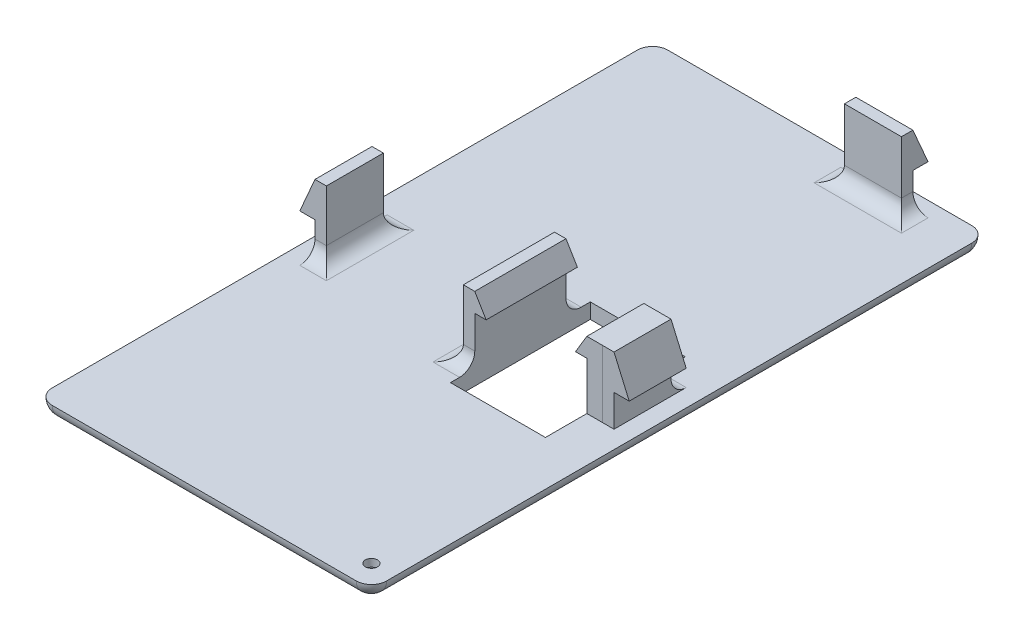
SolidWorks part; units mm, degrees
ref_plane "前视基准面" through (0, 0, 0) normal (0, 0, 1) x (1, 0, 0)
ref_plane "上视基准面" through (0, 0, 0) normal (0, 1, 0) x (1, 0, 0)
ref_plane "右视基准面" through (0, 0, 0) normal (1, 0, 0) x (0, 0, -1)
sketch "草图1" plane through (0, 0, 0) normal (0, 1, 0) x (1, 0, 0)
  line L1 (-22, 43) -> (22, 43)
  line L2 (-22, 43) -> (-22, -38)
  line L3 (-22, -38) -> (22, -38)
  line L4 (22, 43) -> (22, -38)
  dimension "D1" = 44
  dimension "D2" = 81
  dimension "D3" = 22
  dimension "D4" = 43
extrude "凸台-拉伸1" add sketch "草图1" along normal blind 2
fillet "圆角1" radius 2 4 edges at (-22, 0, -2.5) (0, 0, -43) (22, 0, -2.5) (0, 0, 38)
sketch "草图4" plane through (0, 2, 0) normal (0, 1, 0) x (1, 0, 0)
  line L1 (-19.675, 3.75) -> (-18.175, 3.75)
  line L2 (-19.675, 3.75) -> (-19.675, -3.75)
  line L3 (-19.675, -3.75) -> (-18.175, -3.75)
  line L4 (-18.175, 3.75) -> (-18.175, -3.75)
  dimension "D1" = 7.5
  dimension "D2" = 3.75
  dimension "D3" = 1.5
extrude "凸台-拉伸4" add sketch "草图4" along normal blind 8.8
sketch "草图6" plane through (0, 0, 3.75) normal (0, 0, 1) x (1, 0, 0)
  line L0 (-19.675, 10.8) -> (-21.675, 6.2)
  line L1 (-21.675, 6.2) -> (-19.675, 6.2)
  line L2 (-19.675, 10.8) -> (-19.675, 2) construction
  line L3 (-19.675, 6.2) -> (-19.675, 10.8)
  dimension "D1" = 4.6
  dimension "D2" = 2
extrude "凸台-拉伸5" add sketch "草图6" against normal blind 7.5
mirror "镜向2" about plane through (0, 0, 0) normal (1, 0, 0) of "凸台-拉伸4", "凸台-拉伸5"
sketch "草图7" plane through (0, 0, 0) normal (0, -1, 0) x (1, 0, 0)
  line L0 (-20, 38) -> (20, 38) construction
  line L1 (22, 36) -> (22, -41) construction
  circle A0 centre (19, 35) radius 0.8
  dimension "D3" = 1.6
  dimension "D1" = 3
  dimension "D2" = 3
extrude "切除-拉伸1" cut sketch "草图7" against normal blind 8.8
sketch "草图8" plane through (0, 0, 0) normal (0, -1, 0) x (1, 0, 0)
  circle A0 centre (19, 35) radius 2
extrude "切除-拉伸2" cut sketch "草图8" against normal blind 1
sketch "草图10" plane through (0, 2, 0) normal (0, 1, 0) x (1, 0, 0)
  line L0 (22, -36) -> (22, 41) construction
  line L1 (6.75, 41) -> (14.25, 41)
  line L2 (6.75, 41) -> (6.75, 39.5)
  line L3 (6.75, 39.5) -> (14.25, 39.5)
  line L4 (14.25, 41) -> (14.25, 39.5)
  line L5 (20, 43) -> (-20, 43) construction
  dimension "D1" = 7.75
  dimension "D2" = 1.5
  dimension "D3" = 2
  dimension "D4" = 7.5
extrude "凸台-拉伸6" add sketch "草图10" along normal blind 9
sketch "草图11" plane through (14.25, 0, 0) normal (1, 0, 0) x (0, 0, -1)
  line L0 (41, 11) -> (43, 6.4)
  line L1 (43, 6.4) -> (41, 6.4)
  line L2 (41, 11) -> (41, 2) construction
  line L3 (41, 11) -> (41, 6.4)
  dimension "D1" = 4.6
  dimension "D2" = 2
extrude "凸台-拉伸7" add sketch "草图11" against normal blind 7.5
sketch "草图12" plane through (0, 0, 0) normal (0, -1, 0) x (1, 0, 0)
  line L1 (3.5998, 9.2) -> (16.0998, 9.2)
  line L2 (3.5998, 9.2) -> (3.5998, -9.2)
  line L3 (3.5998, -9.2) -> (16.0998, -9.2)
  line L4 (16.0998, 9.2) -> (16.0998, -9.2)
  dimension "D1" = 18.4
  dimension "D2" = 9.2
  dimension "D3" = 12.5
extrude "切除-拉伸3" cut sketch "草图12" against normal blind 7.5
sketch "草图13" plane through (0, 2, 0) normal (0, 1, 0) x (1, 0, 0)
  line L0 (16.0998, -9.2) -> (16.0998, 9.2) construction
  line L1 (18.175, 3.75) -> (16.0998, 3.75)
  line L2 (18.175, 3.75) -> (18.175, -3.7484)
  line L3 (18.175, -3.7484) -> (16.0998, -3.7484)
  line L4 (16.0998, 3.75) -> (16.0998, -3.7484)
extrude "凸台-拉伸8" add sketch "草图13" along normal blind 8.8
sketch "草图14" plane through (0, 0, 3.7484) normal (0, 0, 1) x (1, 0, 0)
  line L0 (16.0998, 10.8) -> (14.5998, 8.3)
  line L1 (14.5998, 8.3) -> (16.0998, 8.3)
  line L2 (16.0998, 10.8) -> (16.0998, 2) construction
  line L3 (16.0998, 8.3) -> (16.0998, 10.8)
  dimension "D1" = 2.5
  dimension "D2" = 1.5
extrude "凸台-拉伸9" add sketch "草图14" against normal blind 7.5
sketch "草图15" plane through (0, 2, 0) normal (0, 1, 0) x (1, 0, 0)
  line L0 (3.5998, 9.2) -> (3.5998, -9.2) construction
  line L1 (3.5998, 6) -> (2.0998, 6)
  line L2 (3.5998, 6) -> (3.5998, -6)
  line L3 (3.5998, -6) -> (2.0998, -6)
  line L4 (2.0998, 6) -> (2.0998, -6)
  dimension "D1" = 1.5
  dimension "D2" = 12
  dimension "D3" = 6
extrude "凸台-拉伸10" add sketch "草图15" along normal blind 8.8
sketch "草图16" plane through (0, 0, 6) normal (0, 0, 1) x (1, 0, 0)
  line L0 (3.5998, 10.8) -> (5.0998, 8.3)
  line L1 (5.0998, 8.3) -> (3.5998, 8.3)
  line L2 (3.5998, 10.8) -> (3.5998, 2) construction
  line L3 (3.5998, 8.3) -> (3.5998, 10.8)
  dimension "D1" = 2.5
  dimension "D2" = 1.5
extrude "凸台-拉伸11" add sketch "草图16" against normal blind 12
fillet "圆角2" radius 2 10 edges at (14.25, 2, -40.25) (6.75, 2, -40.25) (-18.925, 2, -3.75) (-18.925, 2, 3.75) (-18.175, 2, 0) (10.5, 2, -39.5) (2.8498, 2, -6) (2.8498, 2, 6) (17.8874, 2, -3.75) (2.0998, 2, 0)
equation "\"8。8\"=7.5"
